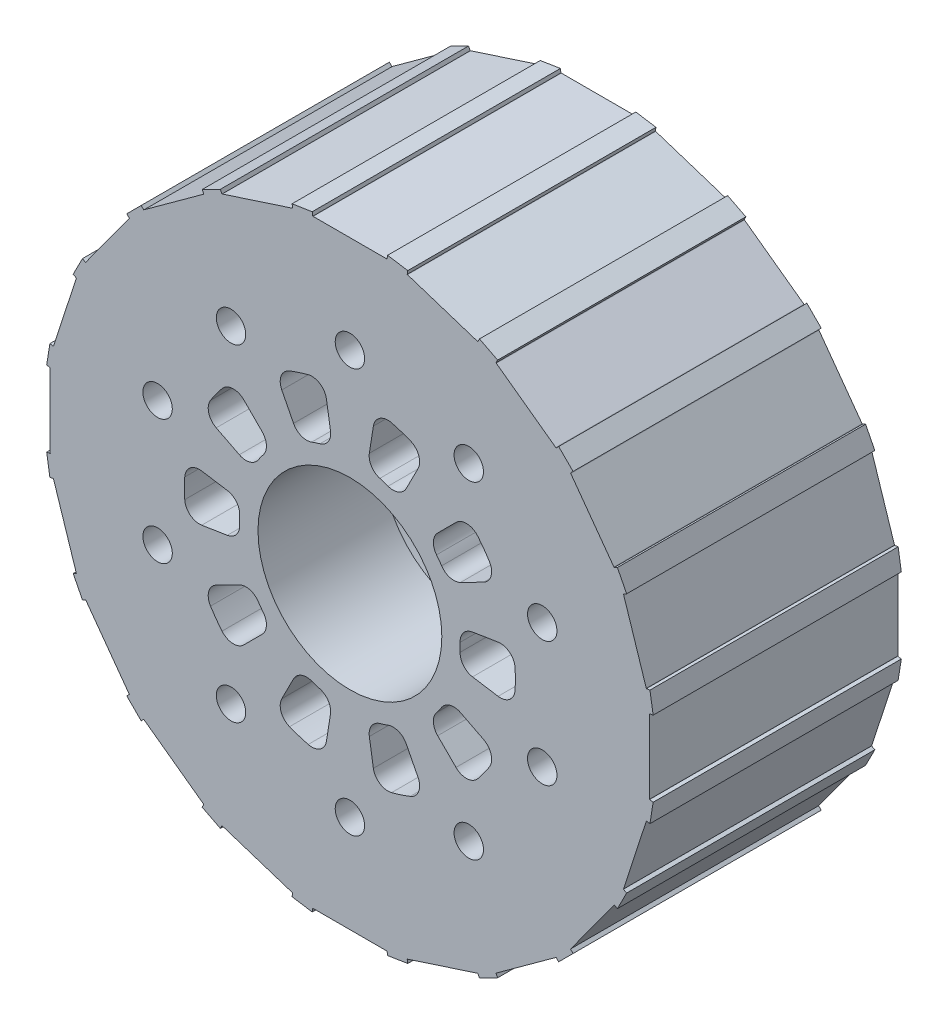
SolidWorks part; units mm, degrees
ref_plane "Ön Düzlem" through (0, 0, 0) normal (0, 0, 1) x (1, 0, 0)
ref_plane "Üst Düzlem" through (0, 0, 0) normal (0, 1, 0) x (1, 0, 0)
ref_plane "Sağ Düzlem" through (0, 0, 0) normal (1, 0, 0) x (0, 0, -1)
sketch "Sketch1" plane through (0, 0, 0) normal (0, 0, 1) x (1, 0, 0)
  line L0 (0, 0) -> (0, 81.5)
  line L1 (10, 81.5) -> (-10, 81.5)
  line L2 (-10, 81.5) -> (-10, 87.5)
  line L3 (10, 81.5) -> (10, 87.5)
  line L4 (15.6743, 80.6013) -> (17.5284, 86.3076)
  line L5 (34.6955, 74.4209) -> (36.5496, 80.1273)
  line L6 (34.6955, 74.4209) -> (15.6743, 80.6013)
  line L7 (39.8143, 71.8127) -> (43.341, 76.6668)
  line L8 (55.9947, 60.057) -> (59.5214, 64.9111)
  line L9 (55.9947, 60.057) -> (39.8143, 71.8127)
  line L10 (60.057, 55.9947) -> (64.9111, 59.5214)
  line L11 (71.8127, 39.8143) -> (76.6668, 43.341)
  line L12 (71.8127, 39.8143) -> (60.057, 55.9947)
  line L13 (74.4209, 34.6955) -> (80.1273, 36.5496)
  line L14 (80.6013, 15.6743) -> (86.3076, 17.5284)
  line L15 (80.6013, 15.6743) -> (74.4209, 34.6955)
  line L16 (81.5, 10) -> (87.5, 10)
  line L17 (81.5, -10) -> (87.5, -10)
  line L18 (81.5, -10) -> (81.5, 10)
  line L19 (80.6013, -15.6743) -> (86.3076, -17.5284)
  line L20 (74.4209, -34.6955) -> (80.1273, -36.5496)
  line L21 (74.4209, -34.6955) -> (80.6013, -15.6743)
  line L22 (71.8127, -39.8143) -> (76.6668, -43.341)
  line L23 (60.057, -55.9947) -> (64.9111, -59.5214)
  line L24 (60.057, -55.9947) -> (71.8127, -39.8143)
  line L25 (55.9947, -60.057) -> (59.5214, -64.9111)
  line L26 (39.8143, -71.8127) -> (43.341, -76.6668)
  line L27 (39.8143, -71.8127) -> (55.9947, -60.057)
  line L28 (34.6955, -74.4209) -> (36.5496, -80.1273)
  line L29 (15.6743, -80.6013) -> (17.5284, -86.3076)
  line L30 (15.6743, -80.6013) -> (34.6955, -74.4209)
  line L31 (10, -81.5) -> (10, -87.5)
  line L32 (-10, -81.5) -> (-10, -87.5)
  line L33 (-10, -81.5) -> (10, -81.5)
  line L34 (-15.6743, -80.6013) -> (-17.5284, -86.3076)
  line L35 (-34.6955, -74.4209) -> (-36.5496, -80.1273)
  line L36 (-34.6955, -74.4209) -> (-15.6743, -80.6013)
  line L37 (-39.8143, -71.8127) -> (-43.341, -76.6668)
  line L38 (-55.9947, -60.057) -> (-59.5214, -64.9111)
  line L39 (-55.9947, -60.057) -> (-39.8143, -71.8127)
  line L40 (-60.057, -55.9947) -> (-64.9111, -59.5214)
  line L41 (-71.8127, -39.8143) -> (-76.6668, -43.341)
  line L42 (-71.8127, -39.8143) -> (-60.057, -55.9947)
  line L43 (-74.4209, -34.6955) -> (-80.1273, -36.5496)
  line L44 (-80.6013, -15.6743) -> (-86.3076, -17.5284)
  line L45 (-80.6013, -15.6743) -> (-74.4209, -34.6955)
  line L46 (-81.5, -10) -> (-87.5, -10)
  line L47 (-81.5, 10) -> (-87.5, 10)
  line L48 (-81.5, 10) -> (-81.5, -10)
  line L49 (-80.6013, 15.6743) -> (-86.3076, 17.5284)
  line L50 (-74.4209, 34.6955) -> (-80.1273, 36.5496)
  line L51 (-74.4209, 34.6955) -> (-80.6013, 15.6743)
  line L52 (-71.8127, 39.8143) -> (-76.6668, 43.341)
  line L53 (-60.057, 55.9947) -> (-64.9111, 59.5214)
  line L54 (-60.057, 55.9947) -> (-71.8127, 39.8143)
  line L55 (-55.9947, 60.057) -> (-59.5214, 64.9111)
  line L56 (-39.8143, 71.8127) -> (-43.341, 76.6668)
  line L57 (-39.8143, 71.8127) -> (-55.9947, 60.057)
  line L58 (-34.6955, 74.4209) -> (-36.5496, 80.1273)
  line L59 (-15.6743, 80.6013) -> (-17.5284, 86.3076)
  line L60 (-15.6743, 80.6013) -> (-34.6955, 74.4209)
  line L61 (34.6955, 74.4209) -> (34.7846, 74.3755)
  line L62 (35.1494, 75.3119) -> (40.2683, 72.7037) construction
  line L63 (39.7252, 71.8581) -> (39.8143, 71.8127)
  line L64 (35.2385, 75.2665) -> (40.1792, 72.7491)
  line L65 (34.7846, 74.3755) -> (35.2385, 75.2665)
  line L66 (55.9947, 60.057) -> (56.0654, 59.9863)
  line L67 (39.7252, 71.8581) -> (40.1792, 72.7491)
  line L68 (34.7846, 74.3755) -> (35.1931, 75.1774) construction
  line L69 (39.7252, 71.8581) -> (40.1338, 72.66) construction
  line L70 (35.1931, 75.1774) -> (40.1338, 72.66) construction
  line L71 (34.6955, 74.4209) -> (35.1494, 75.3119) construction
  line L72 (39.8143, 71.8127) -> (40.2683, 72.7037) construction
  line L73 (56.0654, 59.9863) -> (56.7725, 60.6934)
  line L74 (56.7725, 60.6934) -> (60.6934, 56.7725)
  line L75 (59.9863, 56.0654) -> (60.6934, 56.7725)
  line L76 (59.9863, 56.0654) -> (60.057, 55.9947)
  line L77 (71.8127, 39.8143) -> (71.8581, 39.7252)
  line L78 (71.8581, 39.7252) -> (72.7491, 40.1792)
  line L79 (72.7491, 40.1792) -> (75.2665, 35.2385)
  line L80 (74.3755, 34.7846) -> (75.2665, 35.2385)
  line L81 (74.3755, 34.7846) -> (74.4209, 34.6955)
  line L82 (80.6013, 15.6743) -> (80.6169, 15.5756)
  line L83 (80.6169, 15.5756) -> (81.6046, 15.732)
  line L84 (81.6046, 15.732) -> (82.472, 10.2552)
  line L85 (81.4844, 10.0988) -> (82.472, 10.2552)
  line L86 (81.4844, 10.0988) -> (81.5, 10)
  line L87 (81.5, -10) -> (81.4844, -10.0988)
  line L88 (81.4844, -10.0988) -> (82.472, -10.2552)
  line L89 (82.472, -10.2552) -> (81.6046, -15.732)
  line L90 (80.6169, -15.5756) -> (81.6046, -15.732)
  line L91 (80.6169, -15.5756) -> (80.6013, -15.6743)
  line L92 (74.4209, -34.6955) -> (74.3755, -34.7846)
  line L93 (74.3755, -34.7846) -> (75.2665, -35.2385)
  line L94 (75.2665, -35.2385) -> (72.7491, -40.1792)
  line L95 (71.8581, -39.7252) -> (72.7491, -40.1792)
  line L96 (71.8581, -39.7252) -> (71.8127, -39.8143)
  line L97 (60.057, -55.9947) -> (59.9863, -56.0654)
  line L98 (59.9863, -56.0654) -> (60.6934, -56.7725)
  line L99 (60.6934, -56.7725) -> (56.7725, -60.6934)
  line L100 (56.0654, -59.9863) -> (56.7725, -60.6934)
  line L101 (56.0654, -59.9863) -> (55.9947, -60.057)
  line L102 (39.8143, -71.8127) -> (39.7252, -71.8581)
  line L103 (39.7252, -71.8581) -> (40.1792, -72.7491)
  line L104 (40.1792, -72.7491) -> (35.2385, -75.2665)
  line L105 (34.7846, -74.3755) -> (35.2385, -75.2665)
  line L106 (34.7846, -74.3755) -> (34.6955, -74.4209)
  line L107 (15.6743, -80.6013) -> (15.5756, -80.6169)
  line L108 (15.5756, -80.6169) -> (15.732, -81.6046)
  line L109 (15.732, -81.6046) -> (10.2552, -82.472)
  line L110 (10.0988, -81.4844) -> (10.2552, -82.472)
  line L111 (10.0988, -81.4844) -> (10, -81.5)
  line L112 (-10, -81.5) -> (-10.0988, -81.4844)
  line L113 (-10.0988, -81.4844) -> (-10.2552, -82.472)
  line L114 (-10.2552, -82.472) -> (-15.732, -81.6046)
  line L115 (-15.5756, -80.6169) -> (-15.732, -81.6046)
  line L116 (-15.5756, -80.6169) -> (-15.6743, -80.6013)
  line L117 (-34.6955, -74.4209) -> (-34.7846, -74.3755)
  line L118 (-34.7846, -74.3755) -> (-35.2385, -75.2665)
  line L119 (-35.2385, -75.2665) -> (-40.1792, -72.7491)
  line L120 (-39.7252, -71.8581) -> (-40.1792, -72.7491)
  line L121 (-39.7252, -71.8581) -> (-39.8143, -71.8127)
  line L122 (-55.9947, -60.057) -> (-56.0654, -59.9863)
  line L123 (-56.0654, -59.9863) -> (-56.7725, -60.6934)
  line L124 (-56.7725, -60.6934) -> (-60.6934, -56.7725)
  line L125 (-59.9863, -56.0654) -> (-60.6934, -56.7725)
  line L126 (-59.9863, -56.0654) -> (-60.057, -55.9947)
  line L127 (-71.8127, -39.8143) -> (-71.8581, -39.7252)
  line L128 (-71.8581, -39.7252) -> (-72.7491, -40.1792)
  line L129 (-72.7491, -40.1792) -> (-75.2665, -35.2385)
  line L130 (-74.3755, -34.7846) -> (-75.2665, -35.2385)
  line L131 (-74.3755, -34.7846) -> (-74.4209, -34.6955)
  line L132 (-80.6013, -15.6743) -> (-80.6169, -15.5756)
  line L133 (-80.6169, -15.5756) -> (-81.6046, -15.732)
  line L134 (-81.6046, -15.732) -> (-82.472, -10.2552)
  line L135 (-81.4844, -10.0988) -> (-82.472, -10.2552)
  line L136 (-81.4844, -10.0988) -> (-81.5, -10)
  line L137 (-81.5, 10) -> (-81.4844, 10.0988)
  line L138 (-81.4844, 10.0988) -> (-82.472, 10.2552)
  line L139 (-82.472, 10.2552) -> (-81.6046, 15.732)
  line L140 (-80.6169, 15.5756) -> (-81.6046, 15.732)
  line L141 (-80.6169, 15.5756) -> (-80.6013, 15.6743)
  line L142 (-74.4209, 34.6955) -> (-74.3755, 34.7846)
  line L143 (-74.3755, 34.7846) -> (-75.2665, 35.2385)
  line L144 (-75.2665, 35.2385) -> (-72.7491, 40.1792)
  line L145 (-71.8581, 39.7252) -> (-72.7491, 40.1792)
  line L146 (-71.8581, 39.7252) -> (-71.8127, 39.8143)
  line L147 (-60.057, 55.9947) -> (-59.9863, 56.0654)
  line L148 (-59.9863, 56.0654) -> (-60.6934, 56.7725)
  line L149 (-60.6934, 56.7725) -> (-56.7725, 60.6934)
  line L150 (-56.0654, 59.9863) -> (-56.7725, 60.6934)
  line L151 (-56.0654, 59.9863) -> (-55.9947, 60.057)
  line L152 (-39.8143, 71.8127) -> (-39.7252, 71.8581)
  line L153 (-39.7252, 71.8581) -> (-40.1792, 72.7491)
  line L154 (-40.1792, 72.7491) -> (-35.2385, 75.2665)
  line L155 (-34.7846, 74.3755) -> (-35.2385, 75.2665)
  line L156 (-34.7846, 74.3755) -> (-34.6955, 74.4209)
  line L157 (-15.6743, 80.6013) -> (-15.5756, 80.6169)
  line L158 (-15.5756, 80.6169) -> (-15.732, 81.6046)
  line L159 (-15.732, 81.6046) -> (-10.2552, 82.472)
  line L160 (-10.0988, 81.4844) -> (-10.2552, 82.472)
  line L161 (-10.0988, 81.4844) -> (-10, 81.5)
  line L162 (10, 81.5) -> (10.0988, 81.4844)
  line L163 (10.0988, 81.4844) -> (10.2552, 82.472)
  line L164 (10.2552, 82.472) -> (15.732, 81.6046)
  line L165 (15.5756, 80.6169) -> (15.732, 81.6046)
  line L166 (15.5756, 80.6169) -> (15.6743, 80.6013)
  circle A0 centre (0, 0) radius 25
  arc A2 (10, 87.5) -> (-10, 87.5) centre (0, 38) ccw
  arc A3 (36.5496, 80.1273) -> (17.5284, 86.3076) centre (11.7426, 36.1401) ccw
  arc A4 (59.5214, 64.9111) -> (43.341, 76.6668) centre (22.3358, 30.7426) ccw
  arc A5 (76.6668, 43.341) -> (64.9111, 59.5214) centre (30.7426, 22.3358) ccw
  arc A6 (86.3076, 17.5284) -> (80.1273, 36.5496) centre (36.1401, 11.7426) ccw
  arc A7 (87.5, -10) -> (87.5, 10) centre (38, 0) ccw
  arc A8 (80.1273, -36.5496) -> (86.3076, -17.5284) centre (36.1401, -11.7426) ccw
  arc A9 (64.9111, -59.5214) -> (76.6668, -43.341) centre (30.7426, -22.3358) ccw
  arc A10 (43.341, -76.6668) -> (59.5214, -64.9111) centre (22.3358, -30.7426) ccw
  arc A11 (17.5284, -86.3076) -> (36.5496, -80.1273) centre (11.7426, -36.1401) ccw
  arc A12 (-10, -87.5) -> (10, -87.5) centre (0, -38) ccw
  arc A13 (-36.5496, -80.1273) -> (-17.5284, -86.3076) centre (-11.7426, -36.1401) ccw
  arc A14 (-59.5214, -64.9111) -> (-43.341, -76.6668) centre (-22.3358, -30.7426) ccw
  arc A15 (-76.6668, -43.341) -> (-64.9111, -59.5214) centre (-30.7426, -22.3358) ccw
  arc A16 (-86.3076, -17.5284) -> (-80.1273, -36.5496) centre (-36.1401, -11.7426) ccw
  arc A17 (-87.5, 10) -> (-87.5, -10) centre (-38, 0) ccw
  arc A18 (-80.1273, 36.5496) -> (-86.3076, 17.5284) centre (-36.1401, 11.7426) ccw
  arc A19 (-64.9111, 59.5214) -> (-76.6668, 43.341) centre (-30.7426, 22.3358) ccw
  arc A20 (-43.341, 76.6668) -> (-59.5214, 64.9111) centre (-22.3358, 30.7426) ccw
  arc A21 (-17.5284, 86.3076) -> (-36.5496, 80.1273) centre (-11.7426, 36.1401) ccw
  point P7 (0, 81.5)
  point P107 (0, 0)
  point P231 (0, 0)
  dimension "D1" = 81.5
  dimension "D3" = 50.5
  dimension "D8" = 50
  dimension "D2" = 20
  dimension "D4" = 6
  dimension "D5" = 6
  dimension "D7" = 20
  dimension "D6" = 20
extrude "Boss-Extrude1" add sketch "Sketch1" along normal blind 67.5 contours A0 L1 L161 L160 L159 L158 L157 L60 L156 L155 L154 L153 L152 L57 L151 L150 L149 L148 L147 L54 L146 L145 L144 L143 L142 L51 L141 L140 L139 L138 L137 L48 L136 L135 L134 L133 L132 L45 L131 L130 L129 L128 L127 L42 L126 L125 L124 L123 L122 L39 region at (5, 79.1673, 0)
sketch "Sketch2" plane through (0, 0, 0) normal (0, 0, -1) x (-1, 0, 0)
  circle A0 centre (0, 0) radius 68
extrude "Cut-Extrude1" cut sketch "Sketch2" against normal blind 33.75
sketch "Sketch3" plane through (0, 0, 33.75) normal (0, 0, -1) x (-1, 0, 0)
  line L0 (0, 0) -> (0, 55)
  circle A0 centre (0, 55) radius 4
  circle A1 centre (32.3282, 44.4959) radius 4
  circle A2 centre (52.3081, 16.9959) radius 4
  circle A3 centre (52.3081, -16.9959) radius 4
  circle A4 centre (32.3282, -44.4959) radius 4
  circle A5 centre (0, -55) radius 4
  circle A6 centre (-32.3282, -44.4959) radius 4
  circle A7 centre (-52.3081, -16.9959) radius 4
  circle A8 centre (-52.3081, 16.9959) radius 4
  circle A9 centre (-32.3282, 44.4959) radius 4
  point P24 (0, 0)
  dimension "D1" = 10
extrude "Cut-Extrude2" cut sketch "Sketch3" against normal blind 33.75 contours A0 | A9 | A8 | A1 | A2 | A3 | A4 | A5 | A6 | A7
sketch "Sketch4" plane through (0, 0, 33.75) normal (0, 0, -1) x (-1, 0, 0)
  line L1 (-5.2818, 33.3482) -> (-6.3832, 40.302)
  line L2 (-15.3285, 30.0838) -> (-18.5248, 36.357)
  line L3 (15.3285, 30.0838) -> (18.5248, 36.357)
  line L4 (5.2818, 33.3482) -> (6.3832, 40.302)
  line L5 (30.0838, 15.3285) -> (36.357, 18.5248)
  line L6 (23.8747, 23.8747) -> (28.8531, 28.8531)
  line L7 (33.3482, -5.2818) -> (40.302, -6.3832)
  line L8 (33.3482, 5.2818) -> (40.302, 6.3832)
  line L9 (23.8747, -23.8747) -> (28.8531, -28.8531)
  line L10 (30.0838, -15.3285) -> (36.357, -18.5248)
  line L11 (5.2818, -33.3482) -> (6.3832, -40.302)
  line L12 (15.3285, -30.0838) -> (18.5248, -36.357)
  line L13 (-15.3285, -30.0838) -> (-18.5248, -36.357)
  line L14 (-5.2818, -33.3482) -> (-6.3832, -40.302)
  line L18 (-30.0838, 15.3285) -> (-36.357, 18.5248)
  line L19 (-23.8747, 23.8747) -> (-28.8531, 28.8531)
  line L24 (-30.0838, -15.3285) -> (-36.357, -18.5248)
  line L25 (-23.8747, -23.8747) -> (-28.8531, -28.8531)
  line L26 (-33.3482, 5.2818) -> (-40.302, 6.3832)
  line L27 (-33.3482, -5.2818) -> (-40.302, -6.3832)
  arc A0 (-34.7724, 28.5636) -> (-37.9109, 24.2439) centre (0, 0) ccw
  arc A1 (-23.5616, 18.5702) -> (-24.9422, 16.6699) centre (0, 0) ccw
  arc A6 (-37.9109, 24.2439) -> (-36.357, 18.5248) centre (-34.541, 22.0888) ccw
  arc A7 (-30.0838, 15.3285) -> (-24.9422, 16.6699) centre (-28.2679, 18.8925) ccw
  arc A8 (-23.5616, 18.5702) -> (-23.8747, 23.8747) centre (-26.7031, 21.0462) ccw
  arc A9 (-28.8531, 28.8531) -> (-34.7724, 28.5636) centre (-31.6815, 26.0246) ccw
  arc A10 (-6.3832, 40.302) -> (-11.3422, 43.5472) centre (-10.334, 39.6763) ccw
  arc A11 (-8.1464, 28.8728) -> (-5.2818, 33.3482) centre (-9.2326, 32.7225) ccw
  arc A12 (-11.3422, 43.5472) -> (-16.4204, 41.8971) centre (0, 0) ccw
  arc A13 (-16.4204, 41.8971) -> (-18.5248, 36.357) centre (-14.9608, 38.173) ccw
  arc A14 (-15.3285, 30.0838) -> (-10.3804, 28.1469) centre (-11.7645, 31.8998) ccw
  arc A15 (-8.1464, 28.8728) -> (-10.3804, 28.1469) centre (0, 0) ccw
  arc A16 (18.5248, 36.357) -> (16.4204, 41.8971) centre (14.9608, 38.173) ccw
  arc A17 (10.3804, 28.1469) -> (15.3285, 30.0838) centre (11.7645, 31.8998) ccw
  arc A18 (16.4204, 41.8971) -> (11.3422, 43.5472) centre (0, 0) ccw
  arc A19 (11.3422, 43.5472) -> (6.3832, 40.302) centre (10.334, 39.6763) ccw
  arc A20 (5.2818, 33.3482) -> (8.1464, 28.8728) centre (9.2326, 32.7225) ccw
  arc A21 (10.3804, 28.1469) -> (8.1464, 28.8728) centre (0, 0) ccw
  arc A22 (36.357, 18.5248) -> (37.9109, 24.2439) centre (34.541, 22.0888) ccw
  arc A23 (24.9422, 16.6699) -> (30.0838, 15.3285) centre (28.2679, 18.8925) ccw
  arc A24 (37.9109, 24.2439) -> (34.7724, 28.5636) centre (0, 0) ccw
  arc A25 (34.7724, 28.5636) -> (28.8531, 28.8531) centre (31.6815, 26.0246) ccw
  arc A26 (23.8747, 23.8747) -> (23.5616, 18.5702) centre (26.7031, 21.0462) ccw
  arc A27 (24.9422, 16.6699) -> (23.5616, 18.5702) centre (0, 0) ccw
  arc A28 (40.302, -6.3832) -> (44.9207, -2.6698) centre (40.9278, -2.4325) ccw
  arc A29 (29.977, -1.1745) -> (33.3482, -5.2818) centre (33.9739, -1.3311) ccw
  arc A30 (44.9207, -2.6698) -> (44.9207, 2.6698) centre (0, 0) ccw
  arc A31 (44.9207, 2.6698) -> (40.302, 6.3832) centre (40.9278, 2.4325) ccw
  arc A32 (33.3482, 5.2818) -> (29.977, 1.1745) centre (33.9739, 1.3311) ccw
  arc A33 (29.977, -1.1745) -> (29.977, 1.1745) centre (0, 0) ccw
  arc A34 (28.8531, -28.8531) -> (34.7724, -28.5636) centre (31.6815, -26.0246) ccw
  arc A35 (23.5616, -18.5702) -> (23.8747, -23.8747) centre (26.7031, -21.0462) ccw
  arc A36 (34.7724, -28.5636) -> (37.9109, -24.2439) centre (0, 0) ccw
  arc A37 (37.9109, -24.2439) -> (36.357, -18.5248) centre (34.541, -22.0888) ccw
  arc A38 (30.0838, -15.3285) -> (24.9422, -16.6699) centre (28.2679, -18.8925) ccw
  arc A39 (23.5616, -18.5702) -> (24.9422, -16.6699) centre (0, 0) ccw
  arc A40 (6.3832, -40.302) -> (11.3422, -43.5472) centre (10.334, -39.6763) ccw
  arc A41 (8.1464, -28.8728) -> (5.2818, -33.3482) centre (9.2326, -32.7225) ccw
  arc A42 (11.3422, -43.5472) -> (16.4204, -41.8971) centre (0, 0) ccw
  arc A43 (16.4204, -41.8971) -> (18.5248, -36.357) centre (14.9608, -38.173) ccw
  arc A44 (15.3285, -30.0838) -> (10.3804, -28.1469) centre (11.7645, -31.8998) ccw
  arc A45 (8.1464, -28.8728) -> (10.3804, -28.1469) centre (0, 0) ccw
  arc A46 (-18.5248, -36.357) -> (-16.4204, -41.8971) centre (-14.9608, -38.173) ccw
  arc A47 (-10.3804, -28.1469) -> (-15.3285, -30.0838) centre (-11.7645, -31.8998) ccw
  arc A48 (-16.4204, -41.8971) -> (-11.3422, -43.5472) centre (0, 0) ccw
  arc A49 (-11.3422, -43.5472) -> (-6.3832, -40.302) centre (-10.334, -39.6763) ccw
  arc A50 (-5.2818, -33.3482) -> (-8.1464, -28.8728) centre (-9.2326, -32.7225) ccw
  arc A51 (-10.3804, -28.1469) -> (-8.1464, -28.8728) centre (0, 0) ccw
  arc A52 (-36.357, -18.5248) -> (-37.9109, -24.2439) centre (-34.541, -22.0888) ccw
  arc A53 (-24.9422, -16.6699) -> (-30.0838, -15.3285) centre (-28.2679, -18.8925) ccw
  arc A54 (-37.9109, -24.2439) -> (-34.7724, -28.5636) centre (0, 0) ccw
  arc A55 (-34.7724, -28.5636) -> (-28.8531, -28.8531) centre (-31.6815, -26.0246) ccw
  arc A56 (-23.8747, -23.8747) -> (-23.5616, -18.5702) centre (-26.7031, -21.0462) ccw
  arc A57 (-24.9422, -16.6699) -> (-23.5616, -18.5702) centre (0, 0) ccw
  arc A58 (-40.302, 6.3832) -> (-44.9207, 2.6698) centre (-40.9278, 2.4325) ccw
  arc A59 (-29.977, 1.1745) -> (-33.3482, 5.2818) centre (-33.9739, 1.3311) ccw
  arc A60 (-44.9207, 2.6698) -> (-44.9207, -2.6698) centre (0, 0) ccw
  arc A61 (-44.9207, -2.6698) -> (-40.302, -6.3832) centre (-40.9278, -2.4325) ccw
  arc A62 (-33.3482, -5.2818) -> (-29.977, -1.1745) centre (-33.9739, -1.3311) ccw
  arc A63 (-29.977, 1.1745) -> (-29.977, -1.1745) centre (0, 0) ccw
  point P132 (0, 0)
  dimension "D1" = 4
extrude "Cut-Extrude3" cut sketch "Sketch4" against normal blind 33.75
